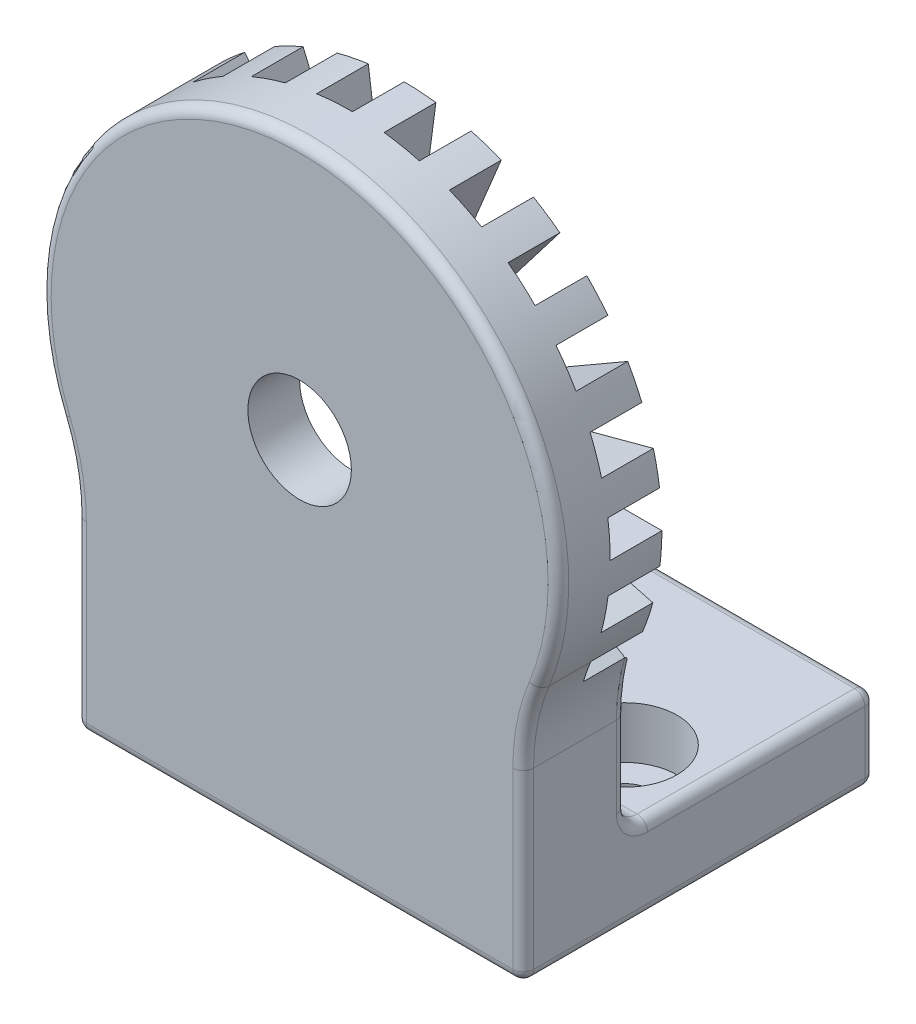
SolidWorks part; units mm, degrees
ref_plane "Front Plane" through (0, 0, 0) normal (0, 0, 1) x (1, 0, 0)
ref_plane "Top Plane" through (0, 0, 0) normal (0, 1, 0) x (1, 0, 0)
ref_plane "Right Plane" through (0, 0, 0) normal (1, 0, 0) x (0, 0, -1)
sketch "Sketch1" plane through (0, 0, 0) normal (0, 0, 1) x (1, 0, 0)
  line L0 (0, 0) -> (0, 25) construction
  line L1 (0, 0) -> (3.2632, 24.7861) construction
  line L2 (0, 0) -> (6.4705, 24.1481) construction
  line L3 (0, 0) -> (9.5671, 23.097) construction
  line L4 (0, 0) -> (12.5, 21.6506) construction
  line L5 (0, 0) -> (15.219, 19.8338) construction
  line L6 (0, 0) -> (17.6777, 17.6777) construction
  line L7 (0, 0) -> (19.8338, 15.219) construction
  line L8 (0, 0) -> (21.6506, 12.5) construction
  line L9 (0, 0) -> (23.097, 9.5671) construction
  line L10 (0, 0) -> (24.1481, 6.4705) construction
  line L11 (0, 0) -> (24.7861, 3.2632) construction
  line L12 (0, 0) -> (25, 0) construction
  line L13 (0, 0) -> (24.7861, -3.2632) construction
  line L14 (0, 0) -> (24.1481, -6.4705) construction
  line L15 (0, 0) -> (23.097, -9.5671) construction
  line L16 (0, 0) -> (21.6506, -12.5) construction
  line L17 (0, 0) -> (19.8338, -15.219) construction
  line L18 (0, 0) -> (17.6777, -17.6777) construction
  line L19 (0, 0) -> (15.219, -19.8338) construction
  line L20 (0, 0) -> (12.5, -21.6506) construction
  line L21 (0, 0) -> (9.5671, -23.097) construction
  line L22 (0, 0) -> (6.4705, -24.1481) construction
  line L23 (0, 0) -> (3.2632, -24.7861) construction
  line L24 (0, 0) -> (0, -25) construction
  line L25 (0, 0) -> (-3.2632, -24.7861) construction
  line L26 (0, 0) -> (-6.4705, -24.1481) construction
  line L27 (0, 0) -> (-9.5671, -23.097) construction
  line L28 (0, 0) -> (-12.5, -21.6506) construction
  line L29 (0, 0) -> (-15.219, -19.8338) construction
  line L30 (0, 0) -> (-17.6777, -17.6777) construction
  line L31 (0, 0) -> (-19.8338, -15.219) construction
  line L32 (0, 0) -> (-21.6506, -12.5) construction
  line L33 (0, 0) -> (-23.097, -9.5671) construction
  line L34 (0, 0) -> (-24.1481, -6.4705) construction
  line L35 (0, 0) -> (-24.7861, -3.2632) construction
  line L36 (0, 0) -> (-25, 0) construction
  line L37 (0, 0) -> (-24.7861, 3.2632) construction
  line L38 (0, 0) -> (-24.1481, 6.4705) construction
  line L39 (0, 0) -> (-23.097, 9.5671) construction
  line L40 (0, 0) -> (-21.6506, 12.5) construction
  line L41 (0, 0) -> (-19.8338, 15.219) construction
  line L42 (0, 0) -> (-17.6777, 17.6777) construction
  line L43 (0, 0) -> (-15.219, 19.8338) construction
  line L44 (0, 0) -> (-12.5, 21.6506) construction
  line L45 (0, 0) -> (-9.5671, 23.097) construction
  line L46 (0, 0) -> (-6.4705, 24.1481) construction
  line L47 (0, 0) -> (-3.2632, 24.7861) construction
  line L48 (-1.5257, 0.1) -> (-24.7992, 3.164)
  line L49 (-1.5257, 0.1) -> (-25, 0.1)
  line L50 (-1.4478, 0.4915) -> (-23.1353, 9.4747)
  line L51 (-1.4478, 0.4915) -> (-24.1223, 6.5671)
  line L52 (-1.2713, 0.8495) -> (-19.8947, 15.1397)
  line L53 (-1.2713, 0.8495) -> (-21.6006, 12.5866)
  line L54 (-1.0081, 1.1495) -> (-15.2984, 19.773)
  line L55 (-1.0081, 1.1495) -> (-17.607, 17.7484)
  line L56 (-0.6763, 1.3713) -> (-9.6595, 23.0587)
  line L57 (-0.6763, 1.3713) -> (-12.4134, 21.7006)
  line L58 (-0.2983, 1.4996) -> (-3.3623, 24.7731)
  line L59 (-0.2983, 1.4996) -> (-6.3739, 24.174)
  line L60 (0.1, 1.5257) -> (3.164, 24.7992)
  line L61 (0.1, 1.5257) -> (0.1, 25)
  line L62 (0.4915, 1.4478) -> (9.4747, 23.1353)
  line L63 (0.4915, 1.4478) -> (6.5671, 24.1223)
  line L64 (0.8495, 1.2713) -> (15.1397, 19.8947)
  line L65 (0.8495, 1.2713) -> (12.5866, 21.6006)
  line L66 (1.1495, 1.0081) -> (19.773, 15.2984)
  line L67 (1.1495, 1.0081) -> (17.7484, 17.607)
  line L68 (1.3713, 0.6763) -> (23.0587, 9.6595)
  line L69 (1.3713, 0.6763) -> (21.7006, 12.4134)
  line L70 (1.4996, 0.2983) -> (24.7731, 3.3623)
  line L71 (1.4996, 0.2983) -> (24.174, 6.3739)
  line L72 (1.5257, -0.1) -> (24.7992, -3.164)
  line L73 (1.5257, -0.1) -> (25, -0.1)
  line L74 (1.4478, -0.4915) -> (23.1353, -9.4747)
  line L75 (1.4478, -0.4915) -> (24.1223, -6.5671)
  line L76 (1.2713, -0.8495) -> (19.8947, -15.1397)
  line L77 (1.2713, -0.8495) -> (21.6006, -12.5866)
  line L78 (1.0081, -1.1495) -> (15.2984, -19.773)
  line L79 (1.0081, -1.1495) -> (17.607, -17.7484)
  line L80 (0.6763, -1.3713) -> (9.6595, -23.0587)
  line L81 (0.6763, -1.3713) -> (12.4134, -21.7006)
  line L82 (0.2983, -1.4996) -> (3.3623, -24.7731)
  line L83 (0.2983, -1.4996) -> (6.3739, -24.174)
  line L84 (-0.1, -1.5257) -> (-3.164, -24.7992)
  line L85 (-0.1, -1.5257) -> (-0.1, -25)
  line L86 (-0.4915, -1.4478) -> (-9.4747, -23.1353)
  line L87 (-0.4915, -1.4478) -> (-6.5671, -24.1223)
  line L88 (-0.8495, -1.2713) -> (-15.1397, -19.8947)
  line L89 (-0.8495, -1.2713) -> (-12.5866, -21.6006)
  line L90 (-1.1495, -1.0081) -> (-19.773, -15.2984)
  line L91 (-1.1495, -1.0081) -> (-17.7484, -17.607)
  line L92 (-1.3713, -0.6763) -> (-23.0587, -9.6595)
  line L93 (-1.3713, -0.6763) -> (-21.7006, -12.4134)
  line L94 (-1.4996, -0.2983) -> (-24.7731, -3.3623)
  line L95 (-1.4996, -0.2983) -> (-24.174, -6.3739)
  circle A0 centre (0, 0) radius 25 construction
  arc A1 (-25, 0.1) -> (-24.7992, 3.164) centre (-1.5257, 0.1) cw
  arc A2 (-24.1223, 6.5671) -> (-23.1353, 9.4747) centre (-1.4478, 0.4915) cw
  arc A3 (-21.6006, 12.5866) -> (-19.8947, 15.1397) centre (-1.2713, 0.8495) cw
  arc A4 (-17.607, 17.7484) -> (-15.2984, 19.773) centre (-1.0081, 1.1495) cw
  arc A5 (-12.4134, 21.7006) -> (-9.6595, 23.0587) centre (-0.6763, 1.3713) cw
  arc A6 (-6.3739, 24.174) -> (-3.3623, 24.7731) centre (-0.2983, 1.4996) cw
  arc A7 (0.1, 25) -> (3.164, 24.7992) centre (0.1, 1.5257) cw
  arc A8 (6.5671, 24.1223) -> (9.4747, 23.1353) centre (0.4915, 1.4478) cw
  arc A9 (12.5866, 21.6006) -> (15.1397, 19.8947) centre (0.8495, 1.2713) cw
  arc A10 (17.7484, 17.607) -> (19.773, 15.2984) centre (1.1495, 1.0081) cw
  arc A11 (21.7006, 12.4134) -> (23.0587, 9.6595) centre (1.3713, 0.6763) cw
  arc A12 (24.174, 6.3739) -> (24.7731, 3.3623) centre (1.4996, 0.2983) cw
  arc A13 (25, -0.1) -> (24.7992, -3.164) centre (1.5257, -0.1) cw
  arc A14 (24.1223, -6.5671) -> (23.1353, -9.4747) centre (1.4478, -0.4915) cw
  arc A15 (21.6006, -12.5866) -> (19.8947, -15.1397) centre (1.2713, -0.8495) cw
  arc A16 (17.607, -17.7484) -> (15.2984, -19.773) centre (1.0081, -1.1495) cw
  arc A17 (12.4134, -21.7006) -> (9.6595, -23.0587) centre (0.6763, -1.3713) cw
  arc A18 (6.3739, -24.174) -> (3.3623, -24.7731) centre (0.2983, -1.4996) cw
  arc A19 (-0.1, -25) -> (-3.164, -24.7992) centre (-0.1, -1.5257) cw
  arc A20 (-6.5671, -24.1223) -> (-9.4747, -23.1353) centre (-0.4915, -1.4478) cw
  arc A21 (-12.5866, -21.6006) -> (-15.1397, -19.8947) centre (-0.8495, -1.2713) cw
  arc A22 (-17.7484, -17.607) -> (-19.773, -15.2984) centre (-1.1495, -1.0081) cw
  arc A23 (-21.7006, -12.4134) -> (-23.0587, -9.6595) centre (-1.3713, -0.6763) cw
  arc A24 (-24.174, -6.3739) -> (-24.7731, -3.3623) centre (-1.4996, -0.2983) cw
  circle A25 centre (0, 0) radius 25
  point P54 (0, 0)
  point P150 (0, 0)
  dimension "D1" = 50
  dimension "D4" = 24
  dimension "D5" = 50
  dimension "D2" = 48
  dimension "D3" = 0.1
extrude "Boss-Extrude1" add sketch "Sketch1" against normal blind 10 contours L48 A25 L49 | L50 A25 L51 | L52 A25 L53 | L54 A25 L55 | L56 A25 L57 | L58 A25 L59 | L60 A25 L61 | L62 A25 L63 | L64 A25 L65 | L66 A25 L67 | L68 A25 L69 | L70 A25 L71 | L72 A25 L73 | L74 A25 L75 | L76 A25 L77 | L78 A25 L79 | L80 A25 L81 | L82 A25 L83 | L86 A25 L87 | L88 A25 L89 | L90 A25 L91 | L92 A25 L93 | L94 A25 L95 | L84 A19 L85 region at (-17.1291, 1.1227, 0) region at (-16.2548, 5.5178, 0) region at (-16.836, -3.3489, 0) region at (-14.2729, 9.5368, 0) region at (-15.3956, -7.5923, 0) region at (-11.3182, 12.906, 0) region at (-12.906, -11.3182, 0) region at (-7.5923, 15.3956, 0) region at (-9.5368, -14.2729, 0) region at (-3.3489, 16.836, 0) region at (-5.5178, -16.2548, 0) region at (1.1227, 17.1291, 0) region at (5.5178, 16.2548, 0) region at (3.3489, -16.836, 0) region at (9.5368, 14.2729, 0) region at (7.5923, -15.3956, 0) region at (12.906, 11.3182, 0) region at (11.3182, -12.906, 0) region at (15.3956, 7.5923, 0) region at (14.2729, -9.5368, 0) region at (16.836, 3.3489, 0) region at (16.2548, -5.5178, 0) region at (17.1291, -1.1227, 0)
extrude "Boss-Extrude2" add sketch "Sketch1<3>" against normal blind 5 contours A25
sketch "Sketch1<3>" plane through (0, 0, 0) normal (0, 0, 1) x (1, 0, 0) same geometry as "Sketch1"
sketch "Sketch2" plane through (0, 0, 0) normal (0, 0, 1) x (1, 0, 0)
  circle A0 centre (0, 0) radius 5
  circle A1 centre (0, 0) radius 17.5
  dimension "D1" = 10
  dimension "D2" = 35
extrude "Cut-Extrude1" cut sketch "Sketch2" against normal through all contours A0 region at (0, 0, 0)
extrude "Boss-Extrude3" add sketch "Sketch2<3>" against normal through all
sketch "Sketch2<3>" plane through (0, 0, 0) normal (0, 0, 1) x (1, 0, 0) same geometry as "Sketch2"
sketch "Sketch3" plane through (0, 0, 0) normal (0, 0, 1) x (1, 0, 0)
  line L0 (21.6005, -12.5865) -> (21.6005, -35)
  line L1 (21.6005, -35) -> (-21.6005, -35)
  line L2 (-21.6005, -35) -> (-21.6005, -12.5865)
  arc A1 (-24.799, 3.164) -> (24.9998, 0.1) centre (0, 0) ccw construction
  arc A5 (-21.6005, -12.5865) -> (21.6005, -12.5865) centre (0, 0) ccw
  dimension "D1" = 10
extrude "Boss-Extrude4" add sketch "Sketch3" against normal blind 10 contours A5 L2 L1 L0 region at (0, -27.7471, 0)
fillet "Fillet1" radius 20 2 edges at (21.6005, -12.5865, -2.5) (-21.6005, -12.5865, -2.5)
sketch "Sketch4" plane through (0, 0, 0) normal (0, 0, 1) x (1, 0, 0)
  line L0 (-22.1146, -12.6524) -> (-15.2052, -8.6633) construction
  line L1 (-21.6005, -35) -> (-21.6005, -12.5865) construction
  line L2 (-22.1146, -12.6524) -> (-21.7071, -12.4172)
  line L3 (-21.6005, -35) -> (-21.6005, -12.5865)
  line L4 (-21.7071, -12.4172) -> (-15.2052, -8.6633) construction
  arc A0 (-21.6005, -12.5865) -> (-19.7728, -15.2982) centre (0, 0) ccw construction
  arc A1 (-21.6005, -12.5865) -> (-19.7728, -15.2982) centre (0, 0) ccw construction
  arc A2 (-21.6005, -12.5865) -> (-21.7071, -12.4172) centre (-24.1024, -14.0444) ccw
  arc A4 (-21.6005, -17.1581) -> (-22.1146, -12.6524) centre (-41.6005, -17.1581) ccw
extrude "Boss-Extrude5" add sketch "Sketch4" against normal blind 10 contours A4 L3 A2 L2 region at (-21.7577, -13.6831, 0)
sketch "Sketch5" plane through (0, 0, 0) normal (0, 0, 1) x (1, 0, 0)
  line L0 (21.6005, -12.5865) -> (21.6005, -35) construction
  line L1 (21.6005, -12.5865) -> (21.6005, -17.1581)
  line L2 (21.6005, -17.1581) -> (21.6005, -35) construction
  arc A0 (23.1114, -9.5323) -> (21.6005, -17.1581) centre (41.6005, -17.1581) ccw construction
  arc A1 (23.1114, -9.5323) -> (21.6005, -17.1581) centre (41.6005, -17.1581) ccw
  arc A2 (23.1114, -9.5323) -> (21.6005, -12.5865) centre (0, 0) cw
extrude "Boss-Extrude6" add sketch "Sketch5" against normal blind 10
sketch "Sketch6" plane through (0, 0, 0) normal (0, 0, 1) x (1, 0, 0)
  line L0 (21.6005, -17.1581) -> (21.6005, -35) construction
  line L1 (-21.6005, -35) -> (21.6005, -35)
  line L2 (-21.6005, -35) -> (-21.6005, -26.9998)
  line L3 (-21.6005, -26.9998) -> (21.6005, -26.9998)
  line L4 (21.6005, -35) -> (21.6005, -26.9998)
  dimension "D1" = 2
extrude "Boss-Extrude7" add sketch "Sketch6" against normal blind 34
fillet "Fillet2" radius 2 1 edges at (0, -26.9998, -10)
fillet "Fillet3" radius 1 20 edges at (0, -35, 0) (-21.6005, -26.0791, 0) (-21.9818, -13.2711, 0) (0, 25, 0) (21.9818, -13.2711, 0) (21.9818, -13.2711, -10) (21.6005, -26.9998, -23) (21.6005, -26.414, -10.5858) (-21.9686, -13.3386, -10) (-21.6005, -21.079, -10) (-21.6005, -26.414, -10.5858) (-21.6005, -35, -17) (21.6005, -35, -17) (21.6005, -26.0791, 0) (21.6005, -21.079, -10) (-21.6005, -26.9998, -23) (0, -35, -34) (0, -26.9998, -34) (21.6005, -30.9999, -34) (-21.6005, -30.9999, -34)
sketch "Sketch7" plane through (0, -35, 0) normal (0, -1, 0) x (-1, 0, 0)
  circle A0 centre (14.25, 17.2) radius 2.5
  circle A1 centre (-14.25, 17.2) radius 2.5
  dimension "D1" = 5
  dimension "D2" = 5
extrude "Cut-Extrude2" cut sketch "Sketch7" against normal up to next
sketch "Sketch8" plane through (0, -35, 0) normal (0, -1, 0) x (-1, 0, 0)
  circle A0 centre (-14.25, 17.2) radius 5
  circle A1 centre (14.25, 17.2) radius 5
  dimension "D1" = 10
  dimension "D2" = 10
extrude "Cut-Extrude3" cut sketch "Sketch8" along normal blind 5 from surface starting at face at (-14.25, -26.9998, -14.7)
sketch "Sketch9" plane through (0, 0, -10) normal (0, 0, -1) x (-1, 0, 0)
  line L0 (6.567, -24.1221) -> (6.6196, -24.315)
  line L1 (3.1893, -24.9974) -> (3.164, -24.799)
  line L2 (0.1, -24.9998) -> (0.1008, -25.1998)
  line L3 (-3.3892, -24.9711) -> (-3.3623, -24.7729)
  line L4 (-6.3738, -24.1738) -> (-6.4248, -24.3672)
  line L5 (-9.7367, -23.243) -> (-9.6594, -23.0585)
  line L6 (-12.4133, -21.7005) -> (-12.5126, -21.8741)
  line L7 (-15.4206, -19.931) -> (-15.2982, -19.7728)
  line L8 (-17.6068, -17.7482) -> (-17.7477, -17.8902)
  line L9 (-20.0537, -15.2607) -> (-19.8946, -15.1396)
  line L10 (-21.6005, -12.5865) -> (-21.7733, -12.6872)
  line L11 (-23.3202, -9.5504) -> (-23.1351, -9.4746)
  line L12 (-24.1221, -6.567) -> (-24.315, -6.6196)
  line L13 (-24.9974, -3.1893) -> (-24.799, -3.164)
  line L14 (-24.9998, -0.1) -> (-25.1998, -0.1008)
  line L15 (-24.9711, 3.3892) -> (-24.7729, 3.3623)
  line L16 (-24.1738, 6.3738) -> (-24.3672, 6.4248)
  line L17 (-23.243, 9.7367) -> (-23.0585, 9.6594)
  line L18 (-21.7005, 12.4133) -> (-21.8741, 12.5126)
  line L19 (-19.931, 15.4206) -> (-19.7728, 15.2982)
  line L20 (-17.7482, 17.6068) -> (-17.8902, 17.7477)
  line L21 (-15.2607, 20.0537) -> (-15.1396, 19.8946)
  line L22 (-12.5865, 21.6005) -> (-12.6872, 21.7733)
  line L23 (-9.5504, 23.3202) -> (-9.4746, 23.1351)
  line L24 (-6.567, 24.1221) -> (-6.6196, 24.315)
  line L25 (-3.1893, 24.9974) -> (-3.164, 24.799)
  line L26 (-0.1, 24.9998) -> (-0.1008, 25.1998)
  line L27 (3.3892, 24.9711) -> (3.3623, 24.7729)
  line L28 (6.3738, 24.1738) -> (6.4248, 24.3672)
  line L29 (9.7367, 23.243) -> (9.6594, 23.0585)
  line L30 (12.4133, 21.7005) -> (12.5126, 21.8741)
  line L31 (15.4206, 19.931) -> (15.2982, 19.7728)
  line L32 (17.6068, 17.7482) -> (17.7477, 17.8902)
  line L33 (20.0537, 15.2607) -> (19.8946, 15.1396)
  line L34 (21.6005, 12.5865) -> (21.7733, 12.6872)
  line L35 (23.3202, 9.5504) -> (23.1351, 9.4746)
  line L36 (24.1221, 6.567) -> (24.315, 6.6196)
  line L37 (24.9974, 3.1893) -> (24.799, 3.164)
  line L38 (24.9998, 0.1) -> (25.1998, 0.1008)
  line L39 (24.9711, -3.3892) -> (24.7729, -3.3623)
  line L40 (24.1738, -6.3738) -> (24.3672, -6.4248)
  line L41 (23.243, -9.7367) -> (23.0585, -9.6594)
  line L42 (21.7005, -12.4133) -> (21.8741, -12.5126)
  line L43 (19.931, -15.4206) -> (19.7728, -15.2982)
  line L44 (17.7482, -17.6068) -> (17.8902, -17.7477)
  line L45 (15.2607, -20.0537) -> (15.1396, -19.8946)
  line L46 (12.5865, -21.6005) -> (12.6872, -21.7733)
  line L47 (9.5504, -23.3202) -> (9.4746, -23.1351)
  arc A1 (3.164, -24.799) -> (6.567, -24.1221) centre (0, 0) ccw construction
  arc A2 (3.1893, -24.9974) -> (6.6196, -24.315) centre (0, 0) ccw
  arc A3 (3.1893, -24.9974) -> (6.6196, -24.315) centre (0, 0) ccw
  arc A4 (3.164, -24.799) -> (6.567, -24.1221) centre (0, 0) ccw
  arc A5 (-3.3892, -24.9711) -> (0.1008, -25.1998) centre (0, 0) ccw
  arc A6 (-3.3623, -24.7729) -> (0.1, -24.9998) centre (0, 0) ccw
  arc A7 (-9.7367, -23.243) -> (-6.4248, -24.3672) centre (0, 0) ccw
  arc A8 (-9.6594, -23.0585) -> (-6.3738, -24.1738) centre (0, 0) ccw
  arc A9 (-15.4206, -19.931) -> (-12.5126, -21.8741) centre (0, 0) ccw
  arc A10 (-15.2982, -19.7728) -> (-12.4133, -21.7005) centre (0, 0) ccw
  arc A11 (-20.0537, -15.2607) -> (-17.7477, -17.8902) centre (0, 0) ccw
  arc A12 (-19.8946, -15.1396) -> (-17.6068, -17.7482) centre (0, 0) ccw
  arc A13 (-23.3202, -9.5504) -> (-21.7733, -12.6872) centre (0, 0) ccw
  arc A14 (-23.1351, -9.4746) -> (-21.6005, -12.5865) centre (0, 0) ccw
  arc A15 (-24.9974, -3.1893) -> (-24.315, -6.6196) centre (0, 0) ccw
  arc A16 (-24.799, -3.164) -> (-24.1221, -6.567) centre (0, 0) ccw
  arc A17 (-24.9711, 3.3892) -> (-25.1998, -0.1008) centre (0, 0) ccw
  arc A18 (-24.7729, 3.3623) -> (-24.9998, -0.1) centre (0, 0) ccw
  arc A19 (-23.243, 9.7367) -> (-24.3672, 6.4248) centre (0, 0) ccw
  arc A20 (-23.0585, 9.6594) -> (-24.1738, 6.3738) centre (0, 0) ccw
  arc A21 (-19.931, 15.4206) -> (-21.8741, 12.5126) centre (0, 0) ccw
  arc A22 (-19.7728, 15.2982) -> (-21.7005, 12.4133) centre (0, 0) ccw
  arc A23 (-15.2607, 20.0537) -> (-17.8902, 17.7477) centre (0, 0) ccw
  arc A24 (-15.1396, 19.8946) -> (-17.7482, 17.6068) centre (0, 0) ccw
  arc A25 (-9.5504, 23.3202) -> (-12.6872, 21.7733) centre (0, 0) ccw
  arc A26 (-9.4746, 23.1351) -> (-12.5865, 21.6005) centre (0, 0) ccw
  arc A27 (-3.1893, 24.9974) -> (-6.6196, 24.315) centre (0, 0) ccw
  arc A28 (-3.164, 24.799) -> (-6.567, 24.1221) centre (0, 0) ccw
  arc A29 (3.3892, 24.9711) -> (-0.1008, 25.1998) centre (0, 0) ccw
  arc A30 (3.3623, 24.7729) -> (-0.1, 24.9998) centre (0, 0) ccw
  arc A31 (9.7367, 23.243) -> (6.4248, 24.3672) centre (0, 0) ccw
  arc A32 (9.6594, 23.0585) -> (6.3738, 24.1738) centre (0, 0) ccw
  arc A33 (15.4206, 19.931) -> (12.5126, 21.8741) centre (0, 0) ccw
  arc A34 (15.2982, 19.7728) -> (12.4133, 21.7005) centre (0, 0) ccw
  arc A35 (20.0537, 15.2607) -> (17.7477, 17.8902) centre (0, 0) ccw
  arc A36 (19.8946, 15.1396) -> (17.6068, 17.7482) centre (0, 0) ccw
  arc A37 (23.3202, 9.5504) -> (21.7733, 12.6872) centre (0, 0) ccw
  arc A38 (23.1351, 9.4746) -> (21.6005, 12.5865) centre (0, 0) ccw
  arc A39 (24.9974, 3.1893) -> (24.315, 6.6196) centre (0, 0) ccw
  arc A40 (24.799, 3.164) -> (24.1221, 6.567) centre (0, 0) ccw
  arc A41 (24.9711, -3.3892) -> (25.1998, 0.1008) centre (0, 0) ccw
  arc A42 (24.7729, -3.3623) -> (24.9998, 0.1) centre (0, 0) ccw
  arc A43 (23.243, -9.7367) -> (24.3672, -6.4248) centre (0, 0) ccw
  arc A44 (23.0585, -9.6594) -> (24.1738, -6.3738) centre (0, 0) ccw
  arc A45 (19.931, -15.4206) -> (21.8741, -12.5126) centre (0, 0) ccw
  arc A46 (19.7728, -15.2982) -> (21.7005, -12.4133) centre (0, 0) ccw
  arc A47 (15.2607, -20.0537) -> (17.8902, -17.7477) centre (0, 0) ccw
  arc A48 (15.1396, -19.8946) -> (17.7482, -17.6068) centre (0, 0) ccw
  arc A49 (9.5504, -23.3202) -> (12.6872, -21.7733) centre (0, 0) ccw
  arc A50 (9.4746, -23.1351) -> (12.5865, -21.6005) centre (0, 0) ccw
  point P101 (0, 0)
  dimension "D1" = 0.2
  dimension "D2" = 24
extrude "Cut-Extrude4" cut sketch "Sketch9" against normal blind 5
sketch "Sketch10" plane through (0, 0, -10) normal (0, 0, -1) x (-1, 0, 0)
  circle A0 centre (0, 0) radius 17.5
  dimension "D1" = 35
extrude "Cut-Extrude5" cut sketch "Sketch10" against normal blind 5
